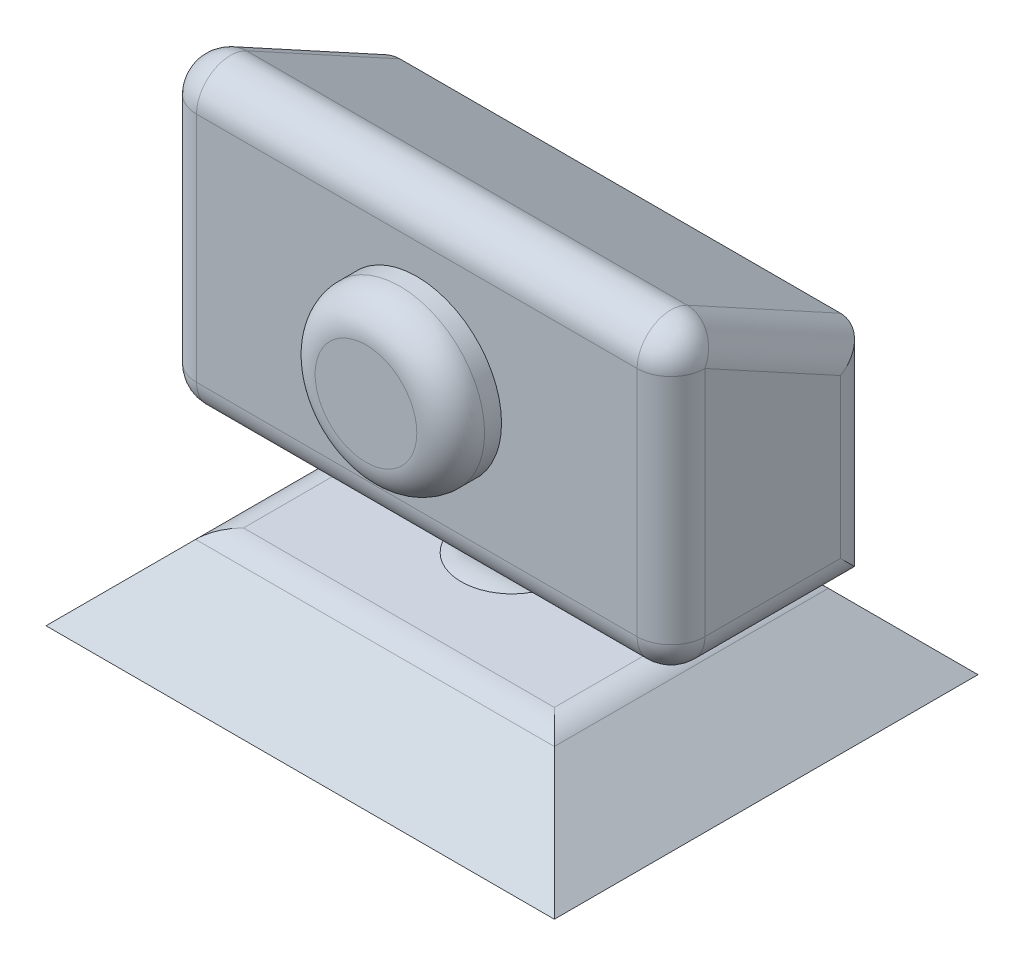
SolidWorks part; units mm, degrees
ref_plane "Front Plane" through (0, 0, 0) normal (0, 0, 1) x (1, 0, 0)
ref_plane "Top Plane" through (0, 0, 0) normal (0, 1, 0) x (1, 0, 0)
ref_plane "Right Plane" through (0, 0, 0) normal (1, 0, 0) x (0, 0, -1)
sketch "Sketch1" plane through (0, 0, 0) normal (0, 1, 0) x (1, 0, 0)
  line L1 (-15, 12.5) -> (15, 12.5)
  line L2 (-15, 12.5) -> (-15, -12.5)
  line L3 (-15, -12.5) -> (15, -12.5)
  line L4 (15, 12.5) -> (15, -12.5)
  line L5 (-15, 12.5) -> (15, -12.5) construction
  line L6 (-15, -12.5) -> (15, 12.5) construction
  point P0 (0, 0)
  dimension "D1" = 30
  dimension "D2" = 25
extrude "Boss-Extrude1" add sketch "Sketch1" along normal blind 5
chamfer "Chamfer1" distance 5 angle 45 4 edges at (0, 5, 12.5) (-15, 5, 0) (0, 5, -12.5) (15, 5, 0)
sketch "Sketch9" plane through (0, 0, 0) normal (0, 0, 1) x (1, 0, 0)
  line L0 (0, 5) -> (0, 8)
  line L1 (-10, 5) -> (10, 5) construction
  line L2 (0, 8) -> (3, 8)
  line L4 (3, 5) -> (0, 5)
  arc A0 (3, 8) -> (3, 5) centre (4.5, 6.5) ccw
  dimension "D1" = 3
revolve "Revolve1" add sketch "Sketch9" angle 360 about L0
sketch "Sketch11" plane through (0, 0, 0) normal (1, 0, 0) x (0, 0, -1)
  line L0 (3, 8) -> (-3, 8) construction
  line L1 (-5.6168, 27.075) -> (6.3832, 20.5325)
  line L3 (-5.6168, 27.075) -> (-5.6168, 8)
  line L4 (-5.6168, 8) -> (6.3832, 8)
  line L5 (6.3832, 20.5325) -> (6.3832, 8)
  line L6 (-5.6168, 27.075) -> (6.3832, 8) construction
  line L7 (-5.6168, 8) -> (0.7839, 23.5853) construction
  point P0 (0, 8)
  point P4 (-0.8771, 19.5409)
  dimension "D1" = 12
extrude "Boss-Extrude4" add sketch "Sketch11" along normal mid plane 30
fillet "Fillet3" radius 2 10 edges at (15, 8, -0.3832) (15, 23.8037, -0.3832) (15, 14.2662, -6.3832) (-15, 23.8037, -0.3832) (-15, 8, -0.3832) (-15, 14.2662, -6.3832) (0, 27.075, 5.6168) (15, 17.5375, 5.6168) (0, 8, 5.6168) (-15, 17.5375, 5.6168)
fillet "Fillet4" radius 2 4 edges at (0, 5, -7.5) (10, 5, 0) (0, 5, 7.5) (-10, 5, 0)
sketch "Sketch12" plane through (0, 0, 5.6168) normal (0, 0, 1) x (1, 0, 0)
  circle A0 centre (0, 16.9136) radius 5
extrude "Boss-Extrude5" add sketch "Sketch12" along normal blind 3
fillet "Fillet5" radius 2 1 edges at (5, 16.9136, 8.6168)
sketch "Sketch13" plane through (0, 0, 8.6168) normal (0, 0, 1) x (1, 0, 0)
  circle A0 centre (0, 16.9136) radius 1.5
